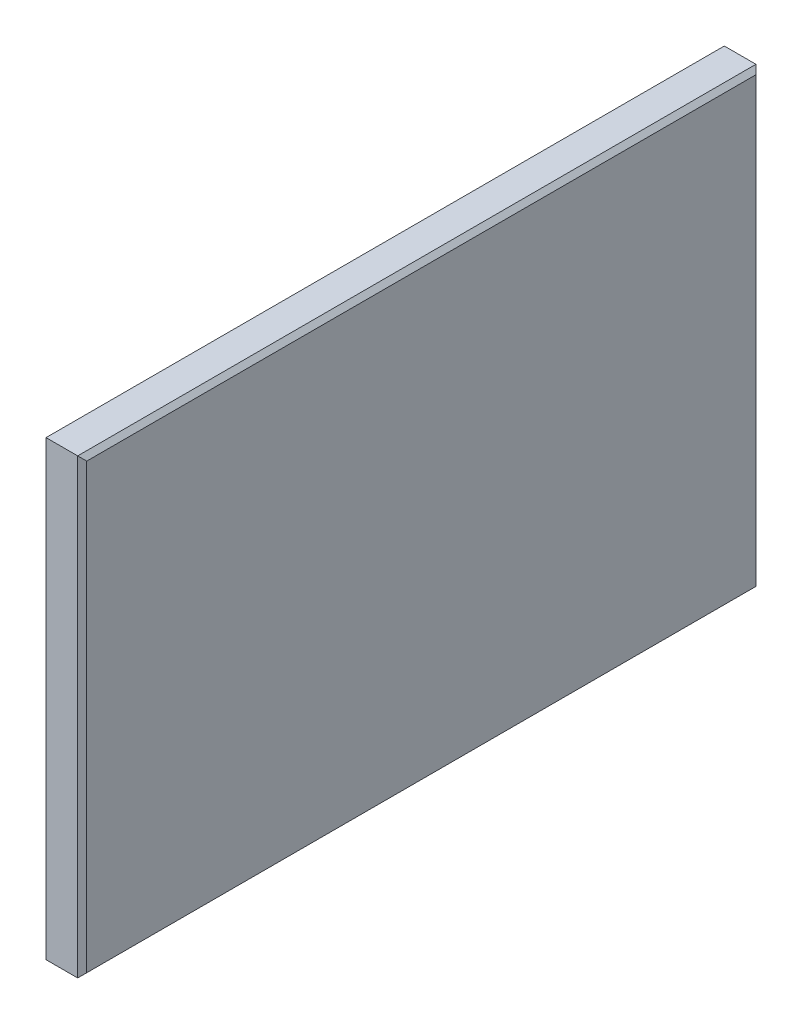
SolidWorks part; units mm, degrees
material "Beech"
ref_plane "Front" through (0, 0, 0) normal (0, 0, 1) x (1, 0, 0)
ref_plane "Top" through (0, 0, 0) normal (0, 1, 0) x (1, 0, 0)
ref_plane "Right" through (0, 0, 0) normal (1, 0, 0) x (0, 0, -1)
ref_axis "side-side" through (80.9, 0, 0) along (-1, 0, 0)
ref_axis "up-down" through (0, 50, 0) along (0, -1, 0)
ref_axis "front-back" through (0, 0, -80.9) along (0, 0, 1)
sketch "Sketch1" plane through (0, 0, 0) normal (1, 0, 0) x (0, 0, -1)
  line L0 (-38.1, 25.4) -> (38.1, -25.4) construction
  line L1 (-38.1, 25.4) -> (38.1, 25.4)
  line L2 (-38.1, 25.4) -> (-38.1, -25.4)
  line L3 (-38.1, -25.4) -> (38.1, -25.4)
  line L4 (38.1, 25.4) -> (38.1, -25.4)
  dimension "D1" = 76.2
  dimension "D2" = 50.8
extrude "Boss-Extrude1" add sketch "Sketch1" along normal blind 4.572
fillet "Fillet1" [suppressed] radius 10.16
chamfer "Chamfer1" distance 0.508 angle 45 8 edges at (4.572, -25.4, 0) (4.572, 0, -38.1) (4.572, 0, 38.1) (4.572, 25.4, 0) (0, -25.4, 0) (0, 0, -38.1) (0, 0, 38.1) (0, 25.4, 0)
